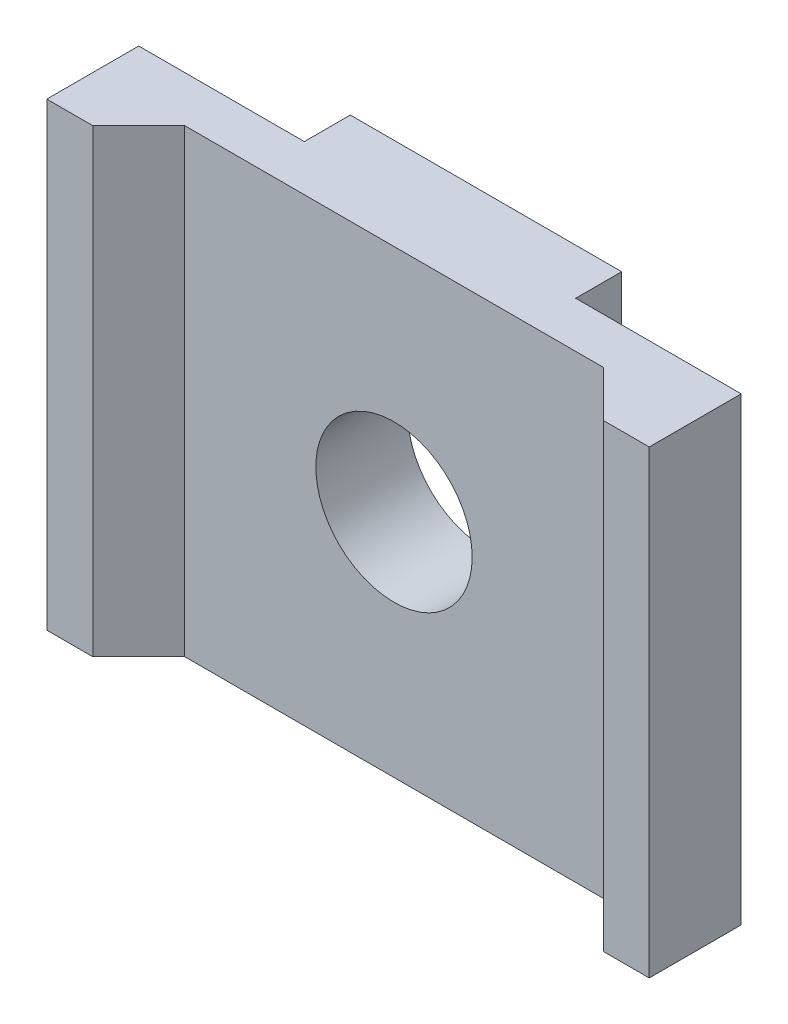
SolidWorks part; units mm, degrees
material "ABS"
ref_plane "Ebene vorne" through (0, 0, 0) normal (0, 0, 1) x (1, 0, 0)
ref_plane "Ebene oben" through (0, 0, 0) normal (0, 1, 0) x (1, 0, 0)
ref_plane "Ebene rechts" through (0, 0, 0) normal (1, 0, 0) x (0, 0, -1)
sketch "Skizze1" plane through (0, 0, 0) normal (0, 1, 0) x (1, 0, 0)
  line L0 (0, 0) -> (-4.55, 0)
  line L1 (-4.55, 0) -> (-4.55, -1)
  line L2 (-4.55, -1) -> (-6.55, -1)
  line L3 (-6.55, -1) -> (-6.55, 1)
  line L4 (-6.55, 1) -> (-2.95, 1)
  line L5 (-2.95, 1) -> (-2.95, 2)
  line L6 (-2.95, 2) -> (0, 2)
  line L7 (0, 2) -> (0, 0)
  dimension "D1" = 2.95
  dimension "D2" = 4.55
  dimension "D3" = 1
  dimension "D4" = 1
  dimension "D5" = 1
  dimension "D6" = 2
extrude "Aufsatz-Linear austragen1" add sketch "Skizze1" along normal blind 10
mirror "Spiegeln1" about plane through (0, 10, -2) normal (-1, 0, 0) of bodies 101
hole_wizard "Durchgangsloch für M31" positions "Skizze2" profile "Skizze3" hole size "M3" standard "DIN" end condition through all
sketch "Skizze2" plane through (0, 0, 0) normal (0, 0, 1) x (1, 0, 0)
  line L0 (0, 0) -> (0, 10) construction
  line L1 (-4.55, 10) -> (4.55, 10) construction
  point P7 (0, 5)
sketch "Skizze3" plane through (0, 5, 0) normal (1, 0, 0) x (0, -1, 0)
  line L0 (0, 0) -> (0, 2)
  line L1 (0, 2) -> (1.7, 2)
  line L2 (1.7, 2) -> (1.7, 0)
  line L5 (1.7, 0) -> (0, 0)
  line L11 (0, -6.35) -> (0, 107.95) construction
  dimension "Bohrerdurchmesser" = 3.4
  dimension "Bohrungstiefe" = 2
draft "Formschräge1" type of draft neutral plane draft angle 45 faces to draft 2 face at (4.55, 5, 0.5) face at (-4.55, 5, 0.5) neutral plane through (0, 10, 0) neutral plane normal (0, 0, 1) parameters "D1"=45
pattern_linear "Lineares Muster1" [suppressed] count 10 spacing 10 of bodies 103
combine bodies "Kombinieren1" [suppressed] operation type add bodies to combine 103 104 105 106 107 108 109 110 111 112 114 115 116 117 119 118 120 121 122 123
